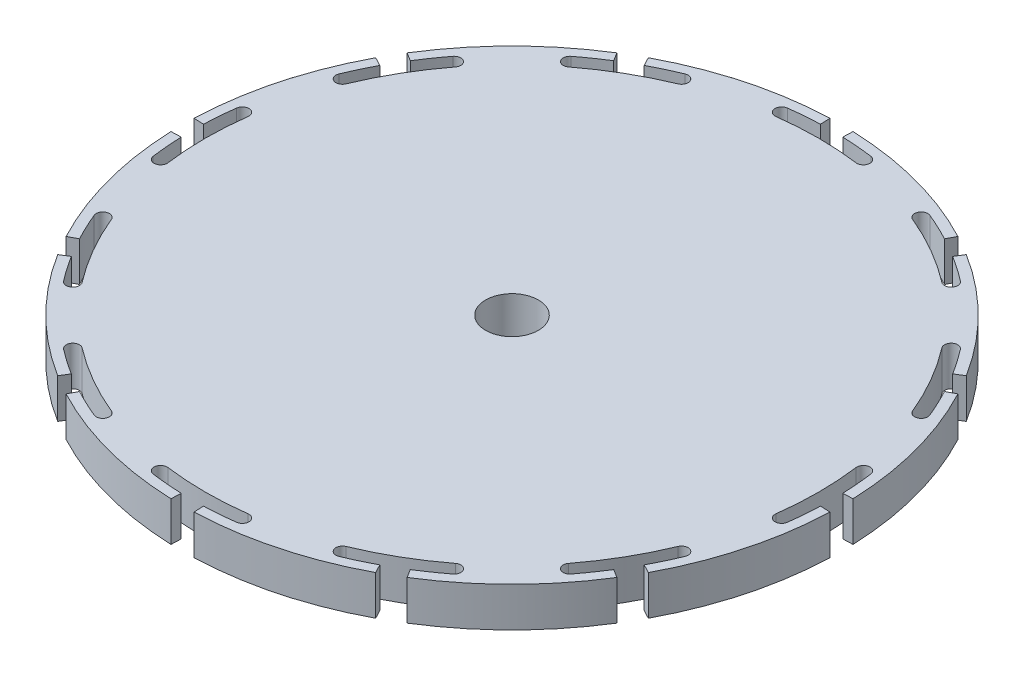
SolidWorks part; units mm, degrees
ref_plane "Front Plane" through (0, 0, 0) normal (0, 0, 1) x (1, 0, 0)
ref_plane "Top Plane" through (0, 0, 0) normal (0, 1, 0) x (1, 0, 0)
ref_plane "Right Plane" through (0, 0, 0) normal (1, 0, 0) x (0, 0, -1)
sketch "Sketch1" plane through (0, 0, 0) normal (0, 1, 0) x (1, 0, 0)
  circle A0 centre (0, 0) radius 50
  dimension "D1" = 100
sketch "Sketch2" plane through (0, 0, 0) normal (0, 1, 0) x (1, 0, 0)
  line L0 (0, 0) -> (0, 50) construction
  line L1 (-1.745, 49.9695) -> (0, 0) construction
  line L2 (0, 0) -> (-6.5263, 49.5722) construction
  line L3 (-1.745, 49.9695) -> (-1.6926, 48.4705)
  line L4 (0, 0) -> (6.5263, 49.5722) construction
  line L5 (1.745, 49.9695) -> (0, 0) construction
  line L6 (1.745, 49.9695) -> (1.6926, 48.4705)
  line L7 (23.4736, 44.1474) -> (22.7694, 42.823)
  line L8 (26.496, 42.4024) -> (25.7011, 41.1303)
  line L9 (42.4024, 26.496) -> (41.1303, 25.7011)
  line L10 (44.1474, 23.4736) -> (42.823, 22.7694)
  line L11 (49.9695, 1.745) -> (48.4705, 1.6926)
  line L12 (49.9695, -1.745) -> (48.4705, -1.6926)
  line L13 (44.1474, -23.4736) -> (42.823, -22.7694)
  line L14 (42.4024, -26.496) -> (41.1303, -25.7011)
  line L15 (26.496, -42.4024) -> (25.7011, -41.1303)
  line L16 (23.4736, -44.1474) -> (22.7694, -42.823)
  line L17 (1.745, -49.9695) -> (1.6926, -48.4705)
  line L18 (-1.745, -49.9695) -> (-1.6926, -48.4705)
  line L19 (-23.4736, -44.1474) -> (-22.7694, -42.823)
  line L20 (-26.496, -42.4024) -> (-25.7011, -41.1303)
  line L21 (-42.4024, -26.496) -> (-41.1303, -25.7011)
  line L22 (-44.1474, -23.4736) -> (-42.823, -22.7694)
  line L23 (-49.9695, -1.745) -> (-48.4705, -1.6926)
  line L24 (-49.9695, 1.745) -> (-48.4705, 1.6926)
  line L25 (-44.1474, 23.4736) -> (-42.823, 22.7694)
  line L26 (-42.4024, 26.496) -> (-41.1303, 25.7011)
  line L27 (-26.496, 42.4024) -> (-25.7011, 41.1303)
  line L28 (-23.4736, 44.1474) -> (-22.7694, 42.823)
  arc A0 (6.0695, 46.1022) -> (-6.0695, 46.1022) centre (0, 0) ccw
  circle A1 centre (0, 0) radius 50 construction
  arc A2 (-1.745, 49.9695) -> (1.745, 49.9695) centre (0, 0) cw
  arc A3 (-1.6926, 48.4705) -> (-6.3305, 48.0851) centre (0, 0) ccw
  arc A4 (-6.0695, 46.1022) -> (-6.3305, 48.0851) centre (-6.2, 47.0936) cw
  arc A5 (6.0695, 46.1022) -> (6.3305, 48.0851) centre (6.2, 47.0936) ccw
  arc A6 (1.6926, 48.4705) -> (6.3305, 48.0851) centre (0, 0) cw
  arc A7 (23.4736, 44.1474) -> (26.496, 42.4024) centre (0, 0) cw
  arc A8 (25.7011, 41.1303) -> (29.5249, 38.4776) centre (0, 0) cw
  arc A9 (28.3074, 36.8909) -> (29.5249, 38.4776) centre (28.9162, 37.6843) ccw
  arc A10 (28.3074, 36.8909) -> (17.7948, 42.9604) centre (0, 0) ccw
  arc A11 (22.7694, 42.823) -> (18.5601, 44.8082) centre (0, 0) ccw
  arc A12 (17.7948, 42.9604) -> (18.5601, 44.8082) centre (18.1775, 43.8843) cw
  arc A13 (42.4024, 26.496) -> (44.1474, 23.4736) centre (0, 0) cw
  arc A14 (42.823, 22.7694) -> (44.8082, 18.5601) centre (0, 0) cw
  arc A15 (42.9604, 17.7948) -> (44.8082, 18.5601) centre (43.8843, 18.1775) ccw
  arc A16 (42.9604, 17.7948) -> (36.8909, 28.3074) centre (0, 0) ccw
  arc A17 (41.1303, 25.7011) -> (38.4776, 29.5249) centre (0, 0) ccw
  arc A18 (36.8909, 28.3074) -> (38.4776, 29.5249) centre (37.6843, 28.9162) cw
  arc A19 (49.9695, 1.745) -> (49.9695, -1.745) centre (0, 0) cw
  arc A20 (48.4705, -1.6926) -> (48.0851, -6.3305) centre (0, 0) cw
  arc A21 (46.1022, -6.0695) -> (48.0851, -6.3305) centre (47.0936, -6.2) ccw
  arc A22 (46.1022, -6.0695) -> (46.1022, 6.0695) centre (0, 0) ccw
  arc A23 (48.4705, 1.6926) -> (48.0851, 6.3305) centre (0, 0) ccw
  arc A24 (46.1022, 6.0695) -> (48.0851, 6.3305) centre (47.0936, 6.2) cw
  arc A25 (44.1474, -23.4736) -> (42.4024, -26.496) centre (0, 0) cw
  arc A26 (41.1303, -25.7011) -> (38.4776, -29.5249) centre (0, 0) cw
  arc A27 (36.8909, -28.3074) -> (38.4776, -29.5249) centre (37.6843, -28.9162) ccw
  arc A28 (36.8909, -28.3074) -> (42.9604, -17.7948) centre (0, 0) ccw
  arc A29 (42.823, -22.7694) -> (44.8082, -18.5601) centre (0, 0) ccw
  arc A30 (42.9604, -17.7948) -> (44.8082, -18.5601) centre (43.8843, -18.1775) cw
  arc A31 (26.496, -42.4024) -> (23.4736, -44.1474) centre (0, 0) cw
  arc A32 (22.7694, -42.823) -> (18.5601, -44.8082) centre (0, 0) cw
  arc A33 (17.7948, -42.9604) -> (18.5601, -44.8082) centre (18.1775, -43.8843) ccw
  arc A34 (17.7948, -42.9604) -> (28.3074, -36.8909) centre (0, 0) ccw
  arc A35 (25.7011, -41.1303) -> (29.5249, -38.4776) centre (0, 0) ccw
  arc A36 (28.3074, -36.8909) -> (29.5249, -38.4776) centre (28.9162, -37.6843) cw
  arc A37 (1.745, -49.9695) -> (-1.745, -49.9695) centre (0, 0) cw
  arc A38 (-1.6926, -48.4705) -> (-6.3305, -48.0851) centre (0, 0) cw
  arc A39 (-6.0695, -46.1022) -> (-6.3305, -48.0851) centre (-6.2, -47.0936) ccw
  arc A40 (-6.0695, -46.1022) -> (6.0695, -46.1022) centre (0, 0) ccw
  arc A41 (1.6926, -48.4705) -> (6.3305, -48.0851) centre (0, 0) ccw
  arc A42 (6.0695, -46.1022) -> (6.3305, -48.0851) centre (6.2, -47.0936) cw
  arc A43 (-23.4736, -44.1474) -> (-26.496, -42.4024) centre (0, 0) cw
  arc A44 (-25.7011, -41.1303) -> (-29.5249, -38.4776) centre (0, 0) cw
  arc A45 (-28.3074, -36.8909) -> (-29.5249, -38.4776) centre (-28.9162, -37.6843) ccw
  arc A46 (-28.3074, -36.8909) -> (-17.7948, -42.9604) centre (0, 0) ccw
  arc A47 (-22.7694, -42.823) -> (-18.5601, -44.8082) centre (0, 0) ccw
  arc A48 (-17.7948, -42.9604) -> (-18.5601, -44.8082) centre (-18.1775, -43.8843) cw
  arc A49 (-42.4024, -26.496) -> (-44.1474, -23.4736) centre (0, 0) cw
  arc A50 (-42.823, -22.7694) -> (-44.8082, -18.5601) centre (0, 0) cw
  arc A51 (-42.9604, -17.7948) -> (-44.8082, -18.5601) centre (-43.8843, -18.1775) ccw
  arc A52 (-42.9604, -17.7948) -> (-36.8909, -28.3074) centre (0, 0) ccw
  arc A53 (-41.1303, -25.7011) -> (-38.4776, -29.5249) centre (0, 0) ccw
  arc A54 (-36.8909, -28.3074) -> (-38.4776, -29.5249) centre (-37.6843, -28.9162) cw
  arc A55 (-49.9695, -1.745) -> (-49.9695, 1.745) centre (0, 0) cw
  arc A56 (-48.4705, 1.6926) -> (-48.0851, 6.3305) centre (0, 0) cw
  arc A57 (-46.1022, 6.0695) -> (-48.0851, 6.3305) centre (-47.0936, 6.2) ccw
  arc A58 (-46.1022, 6.0695) -> (-46.1022, -6.0695) centre (0, 0) ccw
  arc A59 (-48.4705, -1.6926) -> (-48.0851, -6.3305) centre (0, 0) ccw
  arc A60 (-46.1022, -6.0695) -> (-48.0851, -6.3305) centre (-47.0936, -6.2) cw
  arc A61 (-44.1474, 23.4736) -> (-42.4024, 26.496) centre (0, 0) cw
  arc A62 (-41.1303, 25.7011) -> (-38.4776, 29.5249) centre (0, 0) cw
  arc A63 (-36.8909, 28.3074) -> (-38.4776, 29.5249) centre (-37.6843, 28.9162) ccw
  arc A64 (-36.8909, 28.3074) -> (-42.9604, 17.7948) centre (0, 0) ccw
  arc A65 (-42.823, 22.7694) -> (-44.8082, 18.5601) centre (0, 0) ccw
  arc A66 (-42.9604, 17.7948) -> (-44.8082, 18.5601) centre (-43.8843, 18.1775) cw
  arc A67 (-26.496, 42.4024) -> (-23.4736, 44.1474) centre (0, 0) cw
  arc A68 (-22.7694, 42.823) -> (-18.5601, 44.8082) centre (0, 0) cw
  arc A69 (-17.7948, 42.9604) -> (-18.5601, 44.8082) centre (-18.1775, 43.8843) ccw
  arc A70 (-17.7948, 42.9604) -> (-28.3074, 36.8909) centre (0, 0) ccw
  arc A71 (-25.7011, 41.1303) -> (-29.5249, 38.4776) centre (0, 0) ccw
  arc A72 (-28.3074, 36.8909) -> (-29.5249, 38.4776) centre (-28.9162, 37.6843) cw
  point P130 (0, 0)
  dimension "D1" = 15
  dimension "D5" = 12
  dimension "D2" = 2
  dimension "D4" = 1.5
  dimension "D3" = 4
sketch "Sketch3" plane through (0, 0, 0) normal (0, 1, 0) x (1, 0, 0)
  circle A0 centre (0, 0) radius 4
  dimension "D1" = 8
extrude "Boss-Extrude1" add sketch "Sketch1" along normal blind 6
extrude "Cut-Extrude1" cut sketch "Sketch2" along normal through all
extrude "Cut-Extrude2" cut sketch "Sketch3" along normal blind 6
